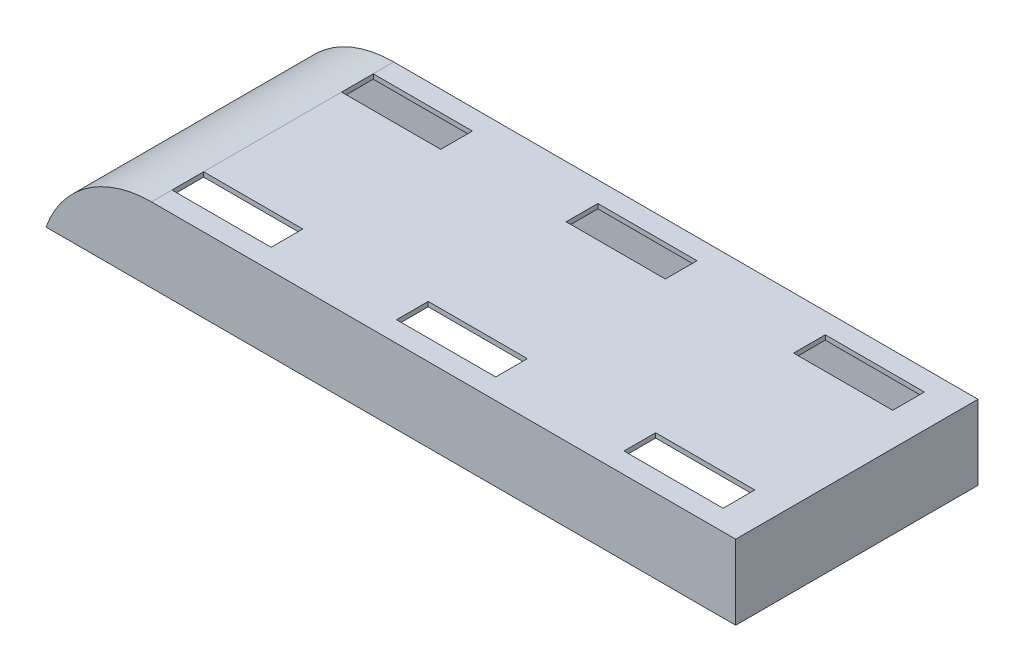
SolidWorks part; units mm, degrees
ref_plane "Front Plane" through (0, 0, 0) normal (0, 0, 1) x (1, 0, 0)
ref_plane "Top Plane" through (0, 0, 0) normal (0, 1, 0) x (1, 0, 0)
ref_plane "Right Plane" through (0, 0, 0) normal (1, 0, 0) x (0, 0, -1)
sketch "Sketch1" plane through (0, 0, 0) normal (0, 1, 0) x (1, 0, 0)
  line L1 (0, 0) -> (939.8, 0)
  line L2 (0, 0) -> (0, 330.2)
  line L3 (0, 330.2) -> (939.8, 330.2)
  line L4 (939.8, 0) -> (939.8, 330.2)
  dimension "D1" = 939.8
  dimension "D2" = 330.2
extrude "Boss-Extrude1" add sketch "Sketch1" along normal blind 101.6
fillet "Fillet1" radius 152.4 1 edges at (0, 101.6, -165.1)
shell "Shell1" thickness 6.35 removed face at (469.9, 0, -165.1)
sketch "Sketch3" plane through (0, 101.6, 0) normal (0, 1, 0) x (1, 0, 0)
  line L0 (449.7211, 27.935) -> (584.8491, 27.935)
  line L17 (584.8491, 27.935) -> (584.8491, 71.115)
  line L18 (143.6841, 165.1) -> (939.8, 165.1) construction
  line L19 (143.6841, 330.2) -> (143.6841, 0) construction
  line L20 (939.8, 0) -> (939.8, 330.2) construction
  line L21 (672.2251, 330.2) -> (672.2251, 0) construction
  line L23 (894.7291, 259.085) -> (759.6011, 259.085)
  line L24 (759.6011, 302.265) -> (759.6011, 259.085)
  line L25 (894.7291, 302.265) -> (759.6011, 302.265)
  line L26 (894.7291, 302.265) -> (894.7291, 259.085)
  line L27 (894.7291, 27.935) -> (894.7291, 71.115)
  line L28 (894.7291, 27.935) -> (759.6011, 27.935)
  line L29 (759.6011, 27.935) -> (759.6011, 71.115)
  line L30 (894.7291, 71.115) -> (759.6011, 71.115)
  line L42 (449.7211, 71.115) -> (584.8491, 71.115)
  line L43 (449.7211, 27.935) -> (449.7211, 71.115)
  line L44 (449.7211, 302.265) -> (449.7211, 259.085)
  line L45 (449.7211, 302.265) -> (584.8491, 302.265)
  line L46 (584.8491, 302.265) -> (584.8491, 259.085)
  line L47 (449.7211, 259.085) -> (584.8491, 259.085)
  line L52 (939.8, 330.2) -> (143.6841, 330.2) construction
  line L57 (143.6841, 302.26) -> (143.6841, 259.08)
  line L58 (143.6841, 302.26) -> (278.8121, 302.26)
  line L59 (278.8121, 302.26) -> (278.8121, 259.08)
  line L60 (143.6841, 259.08) -> (278.8121, 259.08)
  line L61 (143.6841, 27.94) -> (278.8121, 27.94)
  line L62 (278.8121, 27.94) -> (278.8121, 71.12)
  line L63 (143.6841, 71.12) -> (278.8121, 71.12)
  line L64 (143.6841, 27.94) -> (143.6841, 71.12)
  point P10 (827.1651, 259.085)
  dimension "D1" = 45.0709
  dimension "D2" = 154.94
  dimension "D3" = 43.18
  dimension "D4" = 135.128
  dimension "D5" = 93.98
  dimension "D6" = 135.128
  dimension "D7" = 274.33
extrude "Cut-Extrude1" cut sketch "Sketch3" against normal blind 127.762
